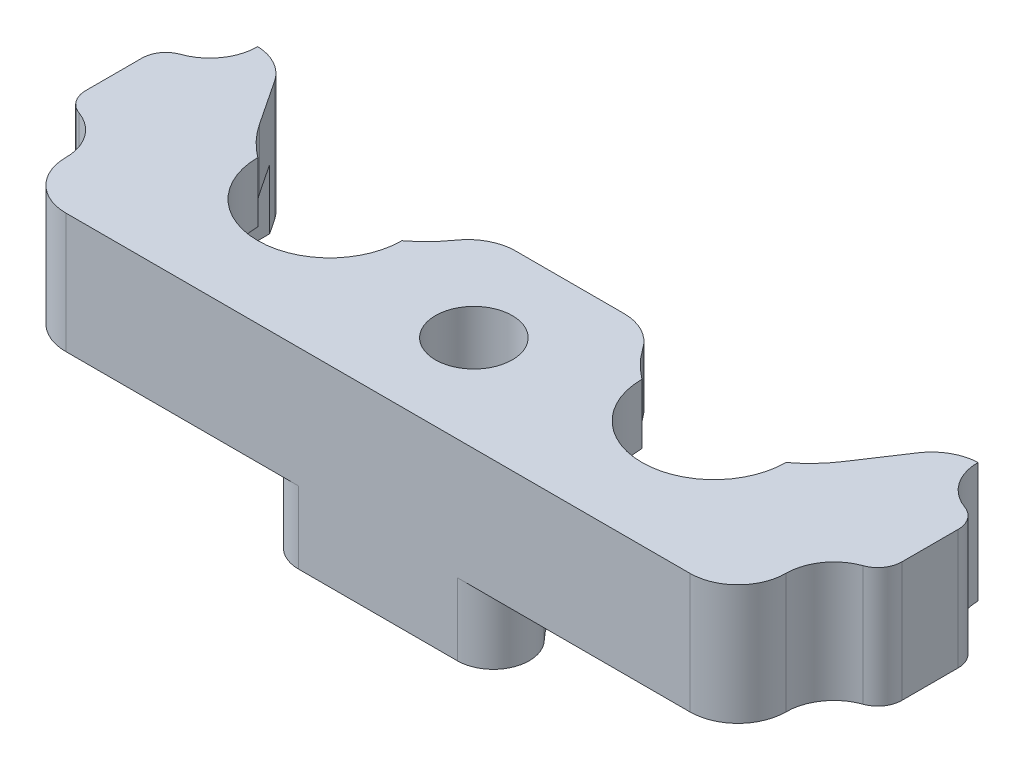
SolidWorks part; units mm, degrees
material "POM 乙缩醛共聚物"
ref_plane "前视基准面" through (0, 0, 0) normal (0, 0, 1) x (1, 0, 0)
ref_plane "上视基准面" through (0, 0, 0) normal (0, 1, 0) x (1, 0, 0)
ref_plane "右视基准面" through (0, 0, 0) normal (1, 0, 0) x (0, 0, -1)
sketch "草图1" plane through (0, 0, 0) normal (0, 1, 0) x (1, 0, 0)
  line L1 (-15, -4) -> (15, -4)
  line L2 (-15, -4) -> (-15, 4)
  line L3 (-15, 4) -> (15, 4) construction
  line L4 (15, -4) -> (15, 4)
  line L5 (0, 4) -> (0, -4) construction
  line L6 (-15, 0) -> (15, 0) construction
  line L7 (-15, 4) -> (15, 4) construction
  line L8 (-15, 4) -> (-15, 6)
  line L9 (-15, 6) -> (15, 6)
  line L10 (15, 4) -> (15, 6)
  circle A0 centre (0, 0) radius 1.6
  point P0 (0, 0)
  dimension "D1" = 3.2
  dimension "D2" = 10
  dimension "D3" = 30
  dimension "D4" = 2
extrude "凸台-拉伸1" add sketch "草图1" along normal blind 5
sketch "草图4" plane through (0, 0, 0) normal (0, -1, 0) x (1, 0, 0)
  line L0 (-15, -6) -> (15, -6) construction
  line L1 (-15, -6) -> (-15, 4) construction
  line L2 (15, 4) -> (15, -6) construction
  line L3 (0, 0) -> (0, -6) construction
  line L4 (15, -6) -> (-15, -6) construction
  line L5 (-8, -6) -> (-8, -2) construction
  line L6 (-13, -6) -> (-13, -2)
  line L7 (-3, -6) -> (-3, -2)
  line L8 (8, -6) -> (8, -2) construction
  line L9 (13, -6) -> (13, -2)
  line L10 (3, -6) -> (3, -2)
  arc A2 (-13, -6) -> (-3, -6) centre (-8, -6) ccw
  arc A3 (-3, -2) -> (-13, -2) centre (-8, -2) ccw
  arc A4 (13, -6) -> (3, -6) centre (8, -6) cw
  arc A5 (3, -2) -> (13, -2) centre (8, -2) cw
  point P13 (-8, -4)
  point P20 (8, -4)
  dimension "D1" = 5
  dimension "D3" = 4
  dimension "D2" = 16
extrude "切除-拉伸1" cut sketch "草图4" against normal blind 2.5
sketch "草图6" plane through (0, 2.5, 0) normal (0, -1, 0) x (1, 0, 0)
  line L0 (0, 0) -> (0, -6) construction
  line L1 (3, -6) -> (-3, -6) construction
  line L2 (-8, -6) -> (-8, -2) construction
  line L3 (-13, -6) -> (-3, -6) construction
  line L4 (-11, -6) -> (-11, -2)
  line L5 (-5, -6) -> (-5, -2)
  line L6 (8, -6) -> (8, -2) construction
  line L7 (11, -6) -> (11, -2)
  line L8 (5, -6) -> (5, -2)
  arc A0 (-11, -6) -> (-5, -6) centre (-8, -6) ccw
  arc A1 (-5, -2) -> (-11, -2) centre (-8, -2) ccw
  arc A2 (-3, -2) -> (-13, -2) centre (-8, -2) ccw construction
  arc A3 (11, -6) -> (5, -6) centre (8, -6) cw
  arc A4 (5, -2) -> (11, -2) centre (8, -2) cw
  point P9 (-8, -4)
  point P19 (8, -4)
  dimension "D1" = 3
extrude "切除-拉伸3" cut sketch "草图6" against normal through all
sketch "草图7" plane through (0, 0, 0) normal (0, -1, 0) x (1, 0, 0)
  line L0 (-11, -6) -> (-5, -6) construction
  line L1 (-12.1667, -3.2361) -> (-14, -6)
  line L2 (0, 0) -> (0, -6) construction
  line L3 (3, -6) -> (-3, -6) construction
  line L4 (-13, -6) -> (-15, -6) construction
  line L5 (-14, -6) -> (-13, -6)
  line L6 (-8, -6) -> (-8, -1) construction
  line L7 (14, -6) -> (13, -6)
  line L8 (12.1667, -3.2361) -> (14, -6)
  arc A0 (-13, -6) -> (-12.1667, -3.2361) centre (-8, -6) ccw
  arc A1 (13, -6) -> (12.1667, -3.2361) centre (8, -6) cw
extrude "切除-拉伸4" cut sketch "草图7" against normal through all
sketch "草图8" plane through (0, 0, 0) normal (0, -1, 0) x (1, 0, 0)
  line L0 (3, -6) -> (-3, -6) construction
  line L1 (-3.4174, -4) -> (3.4174, -4)
  line L2 (-3.4174, -4) -> (-3.4174, -6)
  line L3 (-3.4174, -6) -> (3.4174, -6)
  line L4 (3.4174, -4) -> (3.4174, -6)
  arc A0 (-3, -6) -> (-5, -2) centre (-8, -6) ccw construction
  arc A1 (5, -2) -> (3, -6) centre (8, -6) ccw construction
  dimension "D1" = 2
extrude "切除-拉伸5" cut sketch "草图8" against normal through all
sketch "草图14" plane through (0, 0, 0) normal (0, -1, 0) x (1, 0, 0)
  line L0 (-15, 4) -> (15, 4) construction
  line L1 (0, 0) -> (0, 4) construction
  line L8 (-3, -4) -> (3, -4)
  line L9 (13, -2) -> (13, -4.4924)
  line L10 (15, -6) -> (15, 4)
  line L11 (15, 4) -> (-15, 4)
  line L13 (-15, 4) -> (-15, -6)
  line L14 (-13, -4.4924) -> (-13, -2)
  line L15 (-3, -4) -> (3, -4)
  line L18 (3.3096, 4) -> (-3.3096, 4)
  line L27 (14, -6) -> (15, -6)
  line L28 (14, -6) -> (15, -6)
  line L29 (13, -4.4924) -> (14, -6)
  line L30 (13, -4.4924) -> (14, -6)
  line L31 (-14, -6) -> (-13, -4.4924)
  line L32 (-14, -6) -> (-13, -4.4924)
  line L33 (-15, -6) -> (-14, -6)
  line L34 (-15, -6) -> (-14, -6)
  line L35 (3, -4) -> (3, -2)
  line L36 (3, -4) -> (3, -2)
  line L37 (-3, -2) -> (-3, -4)
  line L38 (-3, -2) -> (-3, -4)
  arc A1 (-3.3096, 4) -> (-4.392, 1.4615) centre (-3.3096, 2.5) ccw
  arc A2 (-3, -2) -> (-13, -2) centre (-8, -2) ccw construction
  arc A3 (3.3096, 4) -> (4.392, 1.4615) centre (3.3096, 2.5) cw
  arc A12 (-3, -2) -> (-13, -2) centre (-8, -2) ccw
  arc A15 (13, -2) -> (3, -2) centre (8, -2) ccw
  arc A27 (-3, -2) -> (-4.392, 1.4615) centre (-8, -2) ccw
  arc A30 (4.392, 1.4615) -> (3, -2) centre (8, -2) ccw
  dimension "D2" = 3
  dimension "D1" = 0
extrude "凸台-拉伸7" add sketch "草图14" along normal blind 3
fillet "圆角2" radius 2 6 edges at (-3, -0.25, -4) (-15, 2.5, 4) (15, 2.5, 4) (3, -0.25, -4) (14, 2.5, -6) (-14, 2.5, -6)
sketch "草图15" plane through (0, 0, 0) normal (0, -1, 0) x (1, 0, 0)
  line L1 (0, 0) -> (0, 4) construction
  line L2 (3.3096, 4) -> (-3.3096, 4) construction
  line L11 (15, 2) -> (15, -6) construction
  line L12 (15, -4) -> (17, -4)
  line L13 (15, -4) -> (15, 0)
  line L14 (15, 0) -> (17, 0)
  line L15 (17, -4) -> (17, 0)
  line L16 (-17, -4) -> (-17, 0)
  line L17 (-15, 0) -> (-17, 0)
  line L18 (-15, -4) -> (-15, 0)
  line L19 (-15, -4) -> (-17, -4)
  dimension "D1" = 2
  dimension "D2" = 2
  dimension "D3" = 4
extrude "凸台-拉伸8" add sketch "草图15" against normal up to surface (5 mm away) up to face at (0, 5, -1.6211)
fillet "圆角3" radius 2 6 edges at (3.4174, 3.75, -4) (-3.4174, 3.75, -4) (-15, 2.5, 0) (15, 2.5, 0) (-15, 2.5, -4) (15, 2.5, -4)
fillet "圆角4" radius 1 4 edges at (-17, 2.5, 0) (-17, 2.5, -4) (17, 2.5, 0) (17, 2.5, -4)
